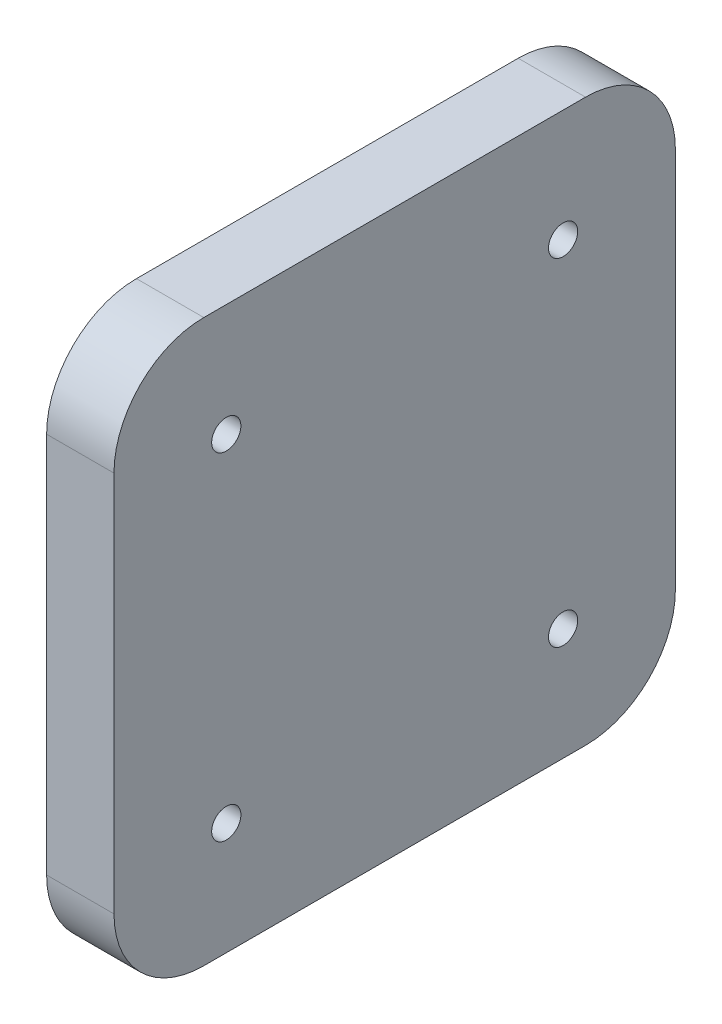
SolidWorks part; units mm, degrees
ref_plane "Front Plane" through (0, 0, 0) normal (0, 0, 1) x (1, 0, 0)
ref_plane "Top Plane" through (0, 0, 0) normal (0, 1, 0) x (1, 0, 0)
ref_plane "Right Plane" through (0, 0, 0) normal (1, 0, 0) x (0, 0, -1)
sketch "Sketch1" plane through (0, 0, 0) normal (1, 0, 0) x (0, 0, -1)
  line L1 (-25, -25) -> (25, -25)
  line L2 (-25, -25) -> (-25, 25)
  line L3 (-25, 25) -> (25, 25)
  line L4 (25, -25) -> (25, 25)
  line L5 (-25, -25) -> (25, 25) construction
  line L6 (-25, 25) -> (25, -25) construction
  circle A0 centre (-15, 15) radius 1.3
  circle A1 centre (15, 15) radius 1.3
  circle A2 centre (15, -15) radius 1.3
  circle A3 centre (-15, -15) radius 1.3
  point P0 (0, 0)
  dimension "D3" = 30
  dimension "D4" = 30
  dimension "D5" = 30
  dimension "D6" = 10
  dimension "D7" = 10
  dimension "D1" = 50
  dimension "D2" = 50
extrude "Boss-Extrude1" add sketch "Sketch1" along normal blind 6
fillet "Fillet1" radius 8 4 edges at (3, -25, -25) (3, -25, 25) (3, 25, 25) (3, 25, -25)
sketch "Sketch2" plane through (0, 0, 0) normal (-1, 0, 0) x (0, 0, 1)
  line L0 (-25, -17) -> (-25, 17) construction
  line L1 (-7.05, -25) -> (-3.05, -25)
  line L2 (-7.05, -25) -> (-7.05, -17)
  line L3 (-7.05, -17) -> (-3.05, -17)
  line L4 (-3.05, -25) -> (-3.05, -17)
  line L5 (3.05, -25) -> (7.05, -25)
  line L6 (3.05, -25) -> (3.05, -17)
  line L7 (3.05, -17) -> (7.05, -17)
  line L8 (7.05, -25) -> (7.05, -17)
  line L10 (17, -25) -> (-17, -25) construction
  dimension "D1" = 8
  dimension "D2" = 8
  dimension "D3" = 4
  dimension "D4" = 4
  dimension "D5" = 6.1
  dimension "D6" = 17.95
  dimension "D7" = 0
extrude "Boss-Extrude2" add sketch "Sketch2" along normal blind 6
fillet "Fillet2" radius 4 4 edges at (-6, -25, 5.05) (-6, -25, -5.05) (-6, -17, -5.05) (-6, -17, 5.05)
sketch "Sketch4" plane through (0, 0, 0) normal (-1, 0, 0) x (0, 0, 1)
  line L0 (-3.05, -17) -> (-7.05, -17) construction
  line L1 (-15, -13) -> (-20, -13)
  line L2 (-15, -13) -> (-15, -5)
  line L3 (-15, -5) -> (-20, -5)
  line L4 (-20, -13) -> (-20, -5)
  line L5 (15, -13) -> (20, -13)
  line L6 (15, -13) -> (15, -5)
  line L7 (15, -5) -> (20, -5)
  line L8 (20, -13) -> (20, -5)
  line L9 (7.05, -17) -> (3.05, -17) construction
  line L12 (25, 17) -> (25, -17) construction
  dimension "D1" = 5
  dimension "D2" = 5
  dimension "D3" = 8
  dimension "D4" = 8
  dimension "D5" = 4
  dimension "D6" = 4
  dimension "D7" = 30
  dimension "D8" = 5
sketch "Sketch6" plane through (0, 0, -7.05) normal (0, 0, -1) x (-1, 0, 0)
  line L1 (2, -17) -> (0, -17) construction
  circle A0 centre (3, -21) radius 1.6
  dimension "D1" = 3
  dimension "D2" = 4
extrude "Cut-Extrude3" cut sketch "Sketch6" against normal blind 36
extrude "Boss-Extrude4" add sketch "Sketch4" along normal blind 5
fillet "Fillet3" radius 3.5 4 edges at (-5, -13, 17.5) (-5, -5, 17.5) (-5, -13, -17.5) (-5, -5, -17.5)
sketch "Sketch5" plane through (0, 0, -20) normal (0, 0, -1) x (-1, 0, 0)
  line L0 (1.5, -5) -> (0, -5) construction
  line L1 (0, -5) -> (0, -13) construction
  circle A0 centre (2.5, -9) radius 0.7
  point P4 (0.75, -5)
  dimension "D1" = 4
  dimension "D2" = 2.5
extrude "Cut-Extrude2" cut sketch "Sketch5" against normal blind 44
chamfer "Chamfer3" distance 1.2 angle 45 10 edges at (-0.75, -5, -15) (-3.9749, -6.0251, -15) (-5, -9, -15) (-3.9749, -11.9749, -15) (-0.75, -13, -15) (-0.75, -5, 15) (-3.9749, -6.0251, 15) (-5, -9, 15) (-3.9749, -11.9749, 15) (-0.75, -13, 15)
